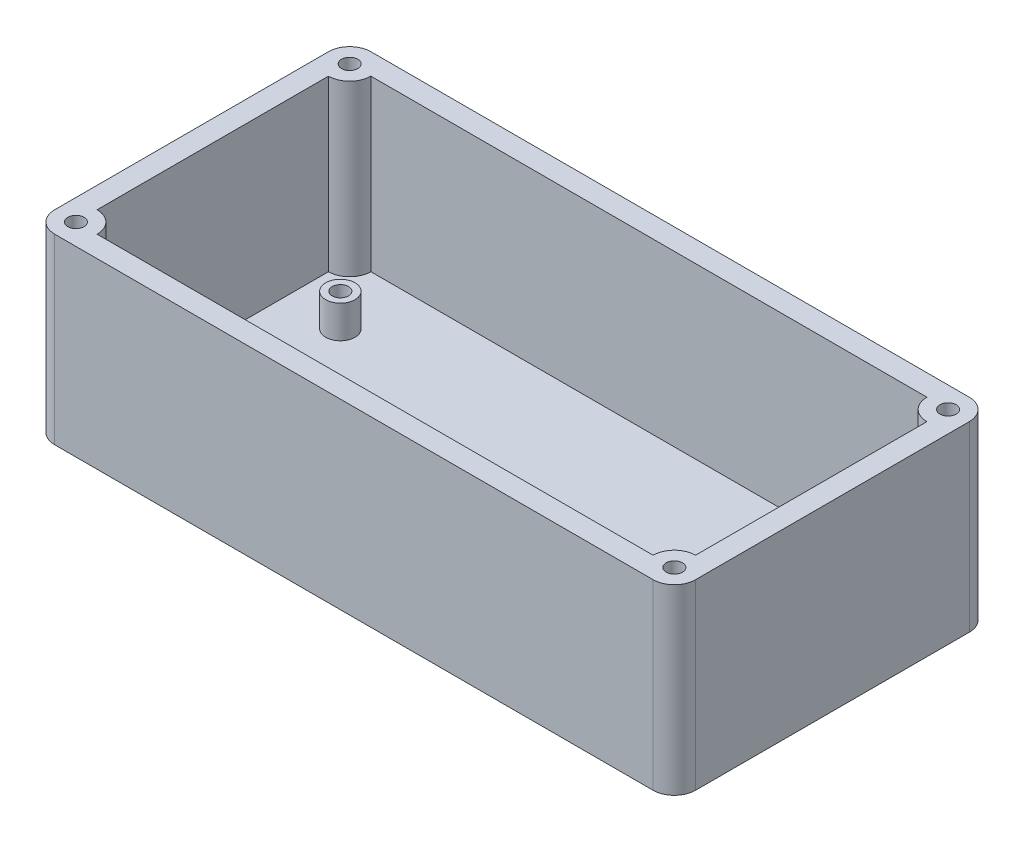
SolidWorks part; units mm, degrees
ref_plane "Front Plane" through (0, 0, 0) normal (0, 0, 1) x (1, 0, 0)
ref_plane "Top Plane" through (0, 0, 0) normal (0, 1, 0) x (1, 0, 0)
ref_plane "Right Plane" through (0, 0, 0) normal (1, 0, 0) x (0, 0, -1)
sketch "Sketch1" plane through (0, 0, 0) normal (0, 1, 0) x (1, 0, 0)
  line L0 (-63.3776, 31.75) -> (63.3776, 31.75)
  line L1 (-47.498, -14.0589) -> (47.498, -14.0589) construction
  line L2 (-47.498, -14.0589) -> (-47.498, 14.0589) construction
  line L3 (-47.498, 14.0589) -> (47.498, 14.0589) construction
  line L4 (47.498, -14.0589) -> (47.498, 14.0589) construction
  line L5 (-47.498, -14.0589) -> (47.498, 14.0589) construction
  line L6 (-47.498, 14.0589) -> (47.498, -14.0589) construction
  line L7 (-58.2976, 26.67) -> (58.2976, 26.67) construction
  line L8 (-58.2976, 26.67) -> (-58.2976, -26.67) construction
  line L9 (-58.2976, -26.67) -> (58.2976, -26.67) construction
  line L10 (58.2976, 26.67) -> (58.2976, -26.67) construction
  line L11 (-58.2976, 26.67) -> (58.2976, -26.67) construction
  line L12 (-58.2976, -26.67) -> (58.2976, 26.67) construction
  line L13 (63.3776, 31.75) -> (63.3776, -31.75)
  line L14 (-63.3776, -31.75) -> (63.3776, -31.75)
  line L15 (-63.3776, 31.75) -> (-63.3776, -31.75)
  circle A0 centre (-47.498, 14.0589) radius 1.5875 construction
  circle A1 centre (-47.498, -14.0589) radius 1.5875 construction
  circle A2 centre (47.498, 14.0589) radius 1.5875
  circle A3 centre (47.498, -14.0589) radius 1.5875
  circle A4 centre (-58.2976, 26.67) radius 1.5875
  circle A5 centre (-58.2976, -26.67) radius 1.5875
  circle A6 centre (58.2976, -26.67) radius 1.5875
  circle A7 centre (58.2976, 26.67) radius 1.5875
  circle A8 centre (-58.2976, 26.67) radius 4.1275
  circle A9 centre (58.2976, 26.67) radius 4.1275
  circle A10 centre (58.2976, -26.67) radius 4.1275
  circle A11 centre (-58.2976, -26.67) radius 4.1275
  point P0 (0, 0)
  point P10 (0, 0)
  point P31 (0, 0)
  dimension "D3" = 3.175
  dimension "D4" = 3.175
  dimension "D1" = 28.1178
  dimension "D2" = 94.996
  dimension "D7" = 53.34
  dimension "D5" = 5.08
  dimension "D6" = 2.54
extrude "Boss-Extrude1" add sketch "Sketch1" along normal blind 2.54 contours L0 L15 L14 L13 A11 A10 A9 A8 A3 A2 | A11 A5 | A5 | A8 A4 | A4 | A9 A7 | A7 | A10 A6 | A2 | A3 | A6 region at (-0.0962, 0, 0) region at (47.498, 0, -14.0589) region at (47.498, 0, 14.0589) region at (-58.2976, 0, -26.67) region at (-58.2976, 0, 26.67) region at (58.2976, 0, -26.67) region at (-62.3083, 0, -26.67) region at (54.2868, 0, -26.67) region at (54.2868, 0, 26.67) region at (-62.3083, 0, 26.67)
sketch "Sketch2" plane through (0, 2.54, 0) normal (0, 1, 0) x (1, 0, 0)
  line L0 (63.3776, 31.75) -> (63.3776, -31.75) construction
  line L1 (-63.3776, -31.75) -> (63.3776, -31.75) construction
  line L2 (-63.3776, 31.75) -> (63.3776, 31.75) construction
  line L3 (-63.3776, 31.75) -> (-63.3776, -31.75) construction
  line L4 (58.2976, 26.67) -> (58.2976, -26.67) construction
  line L5 (-58.2976, -26.67) -> (58.2976, -26.67) construction
  line L6 (-58.2976, 26.67) -> (58.2976, 26.67) construction
  line L7 (-58.2976, 26.67) -> (-58.2976, -26.67) construction
  line L8 (63.3776, 31.75) -> (63.3776, -31.75)
  line L9 (-63.3776, -31.75) -> (63.3776, -31.75)
  line L10 (-63.3776, 31.75) -> (63.3776, 31.75)
  line L11 (-63.3776, 31.75) -> (-63.3776, -31.75)
  line L12 (58.2976, 26.67) -> (58.2976, -26.67)
  line L13 (-58.2976, -26.67) -> (58.2976, -26.67)
  line L14 (-58.2976, 26.67) -> (58.2976, 26.67)
  line L15 (-58.2976, 26.67) -> (-58.2976, -26.67)
  line L16 (-62.4251, 26.67) -> (-62.4251, -26.67)
  line L17 (-58.2976, -30.7975) -> (58.2976, -30.7975)
  line L18 (62.4251, -26.67) -> (62.4251, 26.67)
  line L19 (58.2976, 30.7975) -> (-58.2976, 30.7975)
  circle A0 centre (58.2976, -26.67) radius 4.1275 construction
  circle A1 centre (58.2976, 26.67) radius 4.1275 construction
  circle A2 centre (-58.2976, -26.67) radius 4.1275 construction
  circle A3 centre (-58.2976, 26.67) radius 4.1275 construction
  circle A4 centre (58.2976, -26.67) radius 4.1275
  circle A5 centre (58.2976, 26.67) radius 4.1275
  circle A6 centre (-58.2976, -26.67) radius 4.1275
  circle A7 centre (-58.2976, 26.67) radius 4.1275
  circle A8 centre (58.2976, 26.67) radius 1.5875 construction
  circle A9 centre (58.2976, -26.67) radius 1.5875 construction
  circle A10 centre (-58.2976, -26.67) radius 1.5875 construction
  circle A11 centre (-58.2976, 26.67) radius 1.5875 construction
  circle A12 centre (58.2976, 26.67) radius 1.5875
  circle A13 centre (58.2976, -26.67) radius 1.5875
  circle A14 centre (-58.2976, -26.67) radius 1.5875
  circle A15 centre (-58.2976, 26.67) radius 1.5875
  line M1 (63.3776, 31.75) -> (-63.3776, 31.75)
  line M2 (-63.3776, 31.75) -> (-63.3776, -31.75)
  line M3 (-63.3776, -31.75) -> (63.3776, -31.75)
  line M4 (63.3776, -31.75) -> (63.3776, 31.75)
extrude "Boss-Extrude2" add sketch "Sketch2" along normal blind 33 contours A7 L16 A6 L15 | A14 L15 A6 L13 | A14 L13 A6 L15 | A15 L15 A7 L14 | A15 L14 A7 L15 | A12 L14 A5 L12 | A12 L12 A5 L14 | A13 L13 A4 L12 | A13 L12 A4 L13 | A6 L17 A4 L13 | A5 L12 A4 L18 | A7 L14 A5 L19 region at (59.5027, 2.54, -25.4649) region at (56.3587, 2.54, -24.7311) region at (60.4045, 2.54, 0) region at (0, 2.54, -28.7521) region at (61.1336, 2.54, 23.834) region at (56.3587, 2.54, 24.7311) region at (-56.3587, 2.54, -24.7311) region at (-55.4401, 2.54, -26.7867) region at (0, 2.54, 28.7521) region at (-60.4045, 2.54, 0) region at (-55.4615, 2.54, 29.506) region at (-56.3587, 2.54, 24.7311)
extrude "Cut-Extrude1" cut sketch "Sketch2<4>" against normal through all contours A7 L19 A5 L18 A4 L17 A6 L16 M4 M1 M2 M3 region at (63.2358, 2.54, 0)
sketch "Sketch2<4>" plane through (0, 2.54, 0) normal (0, 1, 0) x (1, 0, 0) same geometry as "Sketch2"
sketch "Sketch4" plane through (0, 2.54, 0) normal (0, 1, 0) x (1, 0, 0)
  circle A0 centre (47.498, 14.0589) radius 1.5875 construction
  circle A1 centre (47.498, -14.0589) radius 1.5875 construction
  circle A2 centre (-47.498, -14.0589) radius 1.5875 construction
  circle A3 centre (-47.498, 14.0589) radius 1.5875 construction
  circle A4 centre (47.498, 14.0589) radius 1.5875
  circle A5 centre (47.498, -14.0589) radius 1.5875
  circle A6 centre (-47.498, -14.0589) radius 1.5875
  circle A7 centre (-47.498, 14.0589) radius 1.5875
  circle A8 centre (-47.498, 14.0589) radius 2.8575
  circle A9 centre (-47.498, -14.0589) radius 2.8575
  circle A10 centre (47.498, -14.0589) radius 2.8575
  circle A11 centre (47.498, 14.0589) radius 2.8575
  dimension "D1" = 1.27
extrude "Boss-Extrude3" add sketch "Sketch4" along normal blind 6.35
